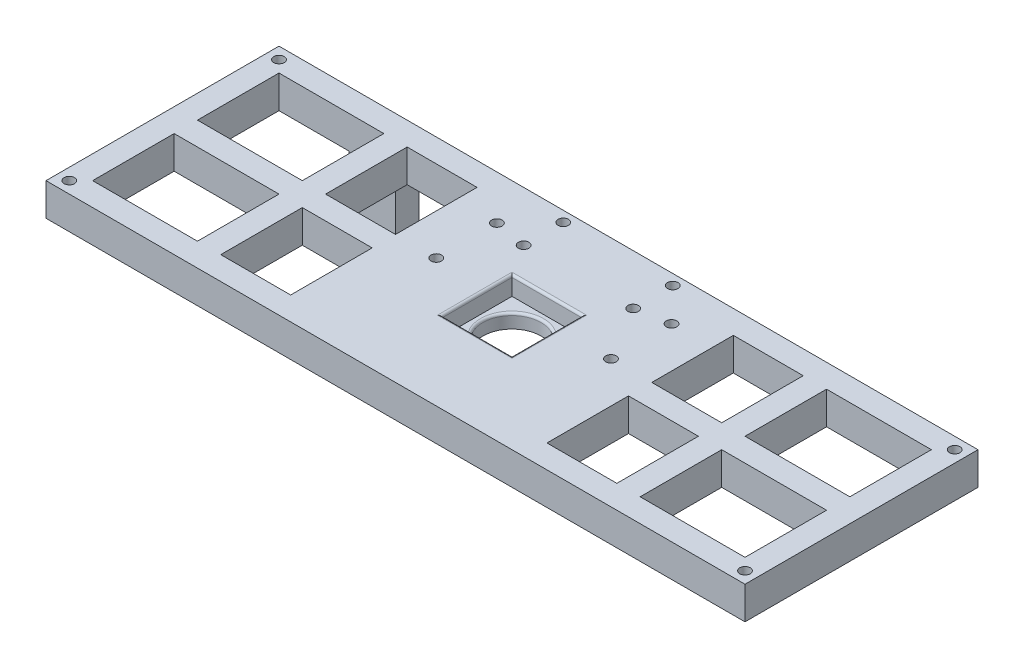
SolidWorks part; units mm, degrees
ref_plane "前视基准面" through (0, 0, 0) normal (0, 0, 1) x (1, 0, 0)
ref_plane "上视基准面" through (0, 0, 0) normal (0, 1, 0) x (1, 0, 0)
ref_plane "右视基准面" through (0, 0, 0) normal (1, 0, 0) x (0, 0, -1)
sketch "草图1" plane through (0, 0, 0) normal (0, 1, 0) x (1, 0, 0)
  line L1 (0, 0) -> (-300, 0)
  line L2 (0, 0) -> (0, 100)
  line L3 (0, 100) -> (-300, 100)
  line L4 (-300, 0) -> (-300, 100)
  dimension "D1" = 300
  dimension "D2" = 100
extrude "凸台-拉伸1" add sketch "草图1" along normal blind 16
sketch "草图2" plane through (0, 16, 0) normal (0, 1, 0) x (1, 0, 0)
  line L0 (-150, 100) -> (-150, 50) construction
  line L1 (0, 100) -> (-300, 100) construction
  line L2 (-300, 50) -> (-150, 50) construction
  line L3 (-300, 100) -> (-300, 0) construction
  line L5 (-165, 65) -> (-135, 65)
  line L6 (-165, 65) -> (-165, 35)
  line L7 (-165, 35) -> (-135, 35)
  line L8 (-135, 65) -> (-135, 35)
  line L9 (-165, 65) -> (-135, 35) construction
  line L10 (-165, 35) -> (-135, 65) construction
  dimension "D1" = 50
  dimension "D2" = 30
  dimension "D3" = 30
extrude "切除-拉伸1" cut sketch "草图2" against normal blind 8
sketch "草图3" plane through (0, 8, 0) normal (0, 1, 0) x (1, 0, 0)
  line L0 (-135, 65) -> (-165, 65) construction
  line L1 (-135, 35) -> (-135, 65) construction
  circle A0 centre (-150, 50) radius 12.5
  dimension "D3" = 25
  dimension "D1" = 15
  dimension "D2" = 15
extrude "切除-拉伸2" cut sketch "草图3" against normal blind 14
sketch "草图4" plane through (0, 16, 0) normal (0, 1, 0) x (1, 0, 0)
  line L0 (-165, 65) -> (-165, 35) construction
  line L1 (-295, 90) -> (-245, 90)
  line L2 (-295, 90) -> (-295, 55)
  line L3 (-295, 55) -> (-245, 55)
  line L4 (-245, 90) -> (-245, 55)
  line L5 (-295, 45) -> (-245, 45)
  line L6 (-295, 45) -> (-295, 10)
  line L7 (-295, 10) -> (-245, 10)
  line L8 (-245, 45) -> (-245, 10)
  line L9 (-235, 90) -> (-185, 90)
  line L10 (-235, 90) -> (-235, 55)
  line L11 (-235, 55) -> (-185, 55)
  line L12 (-185, 90) -> (-185, 55)
  line L13 (-235, 45) -> (-185, 45)
  line L14 (-235, 45) -> (-235, 10)
  line L15 (-235, 10) -> (-185, 10)
  line L16 (-185, 45) -> (-185, 10)
  line L17 (0, 100) -> (-300, 100) construction
  line L18 (-300, 0) -> (0, 0) construction
  line L19 (-300, 100) -> (-300, 0) construction
  line L20 (-150, 100) -> (-150, 73.2626) construction
  line L21 (-5, 10) -> (-55, 10)
  line L22 (-55, 45) -> (-55, 10)
  line L23 (-5, 45) -> (-55, 45)
  line L24 (-5, 45) -> (-5, 10)
  line L25 (-65, 10) -> (-115, 10)
  line L26 (-115, 45) -> (-115, 10)
  line L27 (-65, 45) -> (-115, 45)
  line L28 (-65, 45) -> (-65, 10)
  line L29 (-65, 55) -> (-115, 55)
  line L30 (-115, 90) -> (-115, 55)
  line L31 (-65, 90) -> (-115, 90)
  line L32 (-65, 90) -> (-65, 55)
  line L33 (-5, 55) -> (-55, 55)
  line L34 (-55, 90) -> (-55, 55)
  line L35 (-5, 90) -> (-55, 90)
  line L36 (-5, 90) -> (-5, 55)
  dimension "D1" = 20
  dimension "D2" = 20
  dimension "D3" = 10
  dimension "D4" = 10
  dimension "D5" = 10
  dimension "D6" = 35
  dimension "D7" = 10
  dimension "D8" = 10
  dimension "D9" = 5
  dimension "D10" = 5
  dimension "D11" = 35
  dimension "D12" = 35
  dimension "D13" = 50
  dimension "D14" = 50
  dimension "D15" = 50
  dimension "D16" = 50
extrude "切除-拉伸3" cut sketch "草图4" against normal up to next
sketch "草图7" plane through (-185, 0, 0) normal (-1, 0, 0) x (0, 0, 1)
  line L0 (-45, 0) -> (-10, 0) construction
  line L1 (-10, 0) -> (-10, 16) construction
  line L2 (-10, 16) -> (-45, 16) construction
  line L3 (-45, 16) -> (-45, 0) construction
  line L4 (-90, 0) -> (-55, 0) construction
  line L5 (-55, 0) -> (-55, 16) construction
  line L6 (-55, 16) -> (-90, 16) construction
  line L7 (-90, 16) -> (-90, 0) construction
  line L8 (-45, 0) -> (-10, 0)
  line L9 (-10, 0) -> (-10, 16)
  line L10 (-10, 16) -> (-45, 16)
  line L11 (-45, 16) -> (-45, 0)
  line L12 (-90, 0) -> (-55, 0)
  line L13 (-55, 0) -> (-55, 16)
  line L14 (-55, 16) -> (-90, 16)
  line L15 (-90, 16) -> (-90, 0)
extrude "凸台-拉伸2" add sketch "草图7" along normal blind 20
sketch "草图8" plane through (-115, 0, 0) normal (1, 0, 0) x (0, 0, -1)
  line L0 (10, 0) -> (45, 0) construction
  line L1 (45, 0) -> (45, 16) construction
  line L2 (45, 16) -> (10, 16) construction
  line L3 (10, 16) -> (10, 0) construction
  line L4 (55, 0) -> (90, 0) construction
  line L5 (90, 0) -> (90, 16) construction
  line L6 (90, 16) -> (55, 16) construction
  line L7 (55, 16) -> (55, 0) construction
  line L8 (10, 0) -> (45, 0)
  line L9 (45, 0) -> (45, 16)
  line L10 (45, 16) -> (10, 16)
  line L11 (10, 16) -> (10, 0)
  line L12 (55, 0) -> (90, 0)
  line L13 (90, 0) -> (90, 16)
  line L14 (90, 16) -> (55, 16)
  line L15 (55, 16) -> (55, 0)
extrude "凸台-拉伸3" add sketch "草图8" along normal blind 20
sketch "草图9" plane through (0, 0, 0) normal (0, -1, 0) x (1, 0, 0)
  line L5 (-295, -90) -> (-245, -90) construction
  line L10 (-260, -90) -> (-240, -90)
  line L20 (-260, -90) -> (-260, -100)
  line L21 (-260, -100) -> (-240, -100)
  line L22 (-240, -90) -> (-240, -100)
  line L23 (0, -100) -> (-300, -100) construction
  line L24 (-300, -100) -> (-300, 0) construction
  dimension "D3" = 20
  dimension "D4" = 40
extrude "凸台-拉伸4" add sketch "草图9" along normal blind 25
fillet "圆角1" radius 1 1 edges at (-150, 8, -37.5)
fillet "圆角2" radius 1 4 edges at (-135, 16, -50) (-150, 16, -65) (-150, 16, -35) (-165, 16, -50)
sketch "草图13" plane through (-5, 0, 0) normal (-1, 0, 0) x (0, 0, 1)
  line L0 (-90, 0) -> (-55, 0) construction
  line L1 (-55, 0) -> (-55, 16) construction
  line L2 (-55, 16) -> (-90, 16) construction
  line L3 (-90, 16) -> (-90, 0) construction
  line L4 (-45, 0) -> (-10, 0) construction
  line L5 (-10, 0) -> (-10, 16) construction
  line L6 (-10, 16) -> (-45, 16) construction
  line L7 (-45, 16) -> (-45, 0) construction
  line L8 (-90, 0) -> (-55, 0)
  line L9 (-55, 0) -> (-55, 16)
  line L10 (-55, 16) -> (-90, 16)
  line L11 (-90, 16) -> (-90, 0)
  line L12 (-45, 0) -> (-10, 0)
  line L13 (-10, 0) -> (-10, 16)
  line L14 (-10, 16) -> (-45, 16)
  line L15 (-45, 16) -> (-45, 0)
extrude "凸台-拉伸6" add sketch "草图13" along normal blind 4
sketch "草图14" plane through (-295, 0, 0) normal (1, 0, 0) x (0, 0, -1)
  line L0 (55, 0) -> (90, 0) construction
  line L1 (90, 0) -> (90, 16) construction
  line L2 (90, 16) -> (55, 16) construction
  line L3 (55, 16) -> (55, 0) construction
  line L4 (10, 0) -> (45, 0) construction
  line L5 (45, 0) -> (45, 16) construction
  line L6 (45, 16) -> (10, 16) construction
  line L7 (10, 16) -> (10, 0) construction
  line L8 (55, 0) -> (90, 0)
  line L9 (90, 0) -> (90, 16)
  line L10 (90, 16) -> (55, 16)
  line L11 (55, 16) -> (55, 0)
  line L12 (10, 0) -> (45, 0)
  line L13 (45, 0) -> (45, 16)
  line L14 (45, 16) -> (10, 16)
  line L15 (10, 16) -> (10, 0)
extrude "凸台-拉伸7" add sketch "草图14" along normal blind 4
sketch "草图17" plane through (-291, 0, 0) normal (1, 0, 0) x (0, 0, -1)
  line L0 (10, 16) -> (10, 0) construction
  line L1 (10, 0) -> (45, 0) construction
  line L2 (45, 0) -> (45, 16) construction
  line L3 (45, 16) -> (10, 16) construction
  line L4 (55, 16) -> (55, 0) construction
  line L5 (55, 0) -> (90, 0) construction
  line L6 (90, 0) -> (90, 16) construction
  line L7 (90, 16) -> (55, 16) construction
  line L8 (10, 16) -> (10, 0)
  line L9 (10, 0) -> (45, 0)
  line L10 (45, 0) -> (45, 16)
  line L11 (45, 16) -> (10, 16)
  line L12 (55, 16) -> (55, 0)
  line L13 (55, 0) -> (90, 0)
  line L14 (90, 0) -> (90, 16)
  line L15 (90, 16) -> (55, 16)
extrude "凸台-拉伸8" add sketch "草图17" along normal blind 1
sketch "草图18" plane through (-9, 0, 0) normal (-1, 0, 0) x (0, 0, 1)
  line L0 (-45, 16) -> (-45, 0) construction
  line L1 (-45, 0) -> (-10, 0) construction
  line L2 (-10, 0) -> (-10, 16) construction
  line L3 (-10, 16) -> (-45, 16) construction
  line L4 (-90, 16) -> (-90, 0) construction
  line L5 (-90, 0) -> (-55, 0) construction
  line L6 (-55, 0) -> (-55, 16) construction
  line L7 (-55, 16) -> (-90, 16) construction
  line L8 (-45, 16) -> (-45, 0)
  line L9 (-45, 0) -> (-10, 0)
  line L10 (-10, 0) -> (-10, 16)
  line L11 (-10, 16) -> (-45, 16)
  line L12 (-90, 16) -> (-90, 0)
  line L13 (-90, 0) -> (-55, 0)
  line L14 (-55, 0) -> (-55, 16)
  line L15 (-55, 16) -> (-90, 16)
extrude "凸台-拉伸9" add sketch "草图18" along normal blind 1
sketch "草图19" plane through (0, 16, 0) normal (0, 1, 0) x (1, 0, 0)
  line L0 (-300, 100) -> (-295, 100) construction
  line L1 (0, 100) -> (-300, 100) construction
  line L2 (-295, 100) -> (-295, 95) construction
  line L3 (-150, 100) -> (-150, 83.4567) construction
  line L4 (-300, 50) -> (-202.8605, 50) construction
  line L5 (-300, 100) -> (-300, 0) construction
  line L6 (-150, 0) -> (-150, 22.48) construction
  line L7 (-300, 0) -> (0, 0) construction
  line L8 (-5, 100) -> (-5, 95) construction
  line L9 (0, 100) -> (-5, 100) construction
  circle A0 centre (-295, 95) radius 2.25
  circle A1 centre (-295, 5) radius 2.25
  circle A4 centre (-5, 5) radius 2.25
  circle A5 centre (-5, 95) radius 2.25
  dimension "D3" = 4.5
  dimension "D1" = 5
  dimension "D2" = 5
extrude "切除-拉伸8" cut sketch "草图19" against normal blind 5
sketch "草图20" plane through (0, 0, 0) normal (0, -1, 0) x (1, 0, 0)
  circle A2 centre (-295, -95) radius 2.25 construction
  circle A3 centre (-295, -5) radius 2.25 construction
  circle A6 centre (-295, -95) radius 2.25
  circle A7 centre (-295, -5) radius 2.25
  circle A8 centre (-5, -95) radius 2.25 construction
  circle A9 centre (-5, -5) radius 2.25 construction
  circle A10 centre (-5, -95) radius 2.25
  circle A11 centre (-5, -5) radius 2.25
extrude "切除-拉伸9" cut sketch "草图20" against normal blind 7
extrude "切除-拉伸10" cut sketch "草图21" against normal blind 5
sketch "草图21" plane through (-100.2762, 16, -200.0918) normal (0, 1, 0) x (-0.0018, 0, -1)
  circle A4 centre (-104.5433, 26.4163) radius 1.45
  circle A5 centre (-121.5433, 26.4476) radius 1.45
  circle A6 centre (-121.4568, 73.4475) radius 1.45
  circle A7 centre (-104.4568, 73.4162) radius 1.45
sketch "草图22" plane through (0, 16, 0) normal (0, 1, 0) x (1, 0, 0)
  circle A0 centre (-173.5, 95.5) radius 2.25
  circle A1 centre (-173.5, 78.5) radius 2.25
  circle A2 centre (-126.5, 95.5) radius 2.25
  circle A3 centre (-126.5, 78.5) radius 2.25
  dimension "D1" = 4.5
  dimension "D2" = 4.5
  dimension "D3" = 4.5
  dimension "D4" = 4.5
extrude "切除-拉伸11" cut sketch "草图22" against normal blind 5
extrude "切除-拉伸12" cut sketch "草图23" against normal blind 5
sketch "草图23" plane through (-100.2762, 16, -200.0918) normal (0, 1, 0) x (-0.0018, 0, -1)
  circle A4 centre (-119.0691, 12.4622) radius 1.45
  circle A5 centre (-145.069, 12.51) radius 1.45
  circle A6 centre (-144.931, 87.4716) radius 1.45
  circle A7 centre (-118.9311, 87.4237) radius 1.45
sketch "草图24" plane through (0, 16, 0) normal (0, 1, 0) x (1, 0, 0)
  circle A0 centre (-187.4808, 81) radius 2.25
  circle A1 centre (-187.4808, 55) radius 2.25
  circle A2 centre (-112.5192, 81) radius 2.25
  circle A3 centre (-112.5192, 55) radius 2.25
  dimension "D1" = 4.5
  dimension "D2" = 4.5
  dimension "D3" = 4.5
  dimension "D4" = 4.5
extrude "切除-拉伸13" cut sketch "草图24" against normal blind 5
sketch "草图26" plane through (0, 0, 0) normal (0, -1, 0) x (1, 0, 0)
  line L12 (-260, -90) -> (-290, -90)
  line L13 (-290, -90) -> (-290, -55)
  line L14 (-290, -55) -> (-245, -55)
  line L15 (-245, -55) -> (-245, -90)
  line L16 (-245, -90) -> (-240, -90)
  line L17 (-240, -90) -> (-240, -100)
  line L18 (-240, -100) -> (0, -100)
  line L19 (0, -100) -> (0, 0)
  line L20 (0, 0) -> (-300, 0)
  line L21 (-300, 0) -> (-300, -100)
  line L22 (-300, -100) -> (-260, -100)
  line L23 (-260, -100) -> (-260, -90)
  line L24 (-260, -90) -> (-290, -90)
  line L25 (-290, -90) -> (-290, -55)
  line L26 (-290, -55) -> (-245, -55)
  line L27 (-245, -55) -> (-245, -90)
  line L28 (-245, -90) -> (-240, -90)
  line L29 (-240, -90) -> (-240, -100)
  line L30 (-240, -100) -> (0, -100)
  line L31 (0, -100) -> (0, 0)
  line L32 (0, 0) -> (-300, 0)
  line L33 (-300, 0) -> (-300, -100)
  line L34 (-300, -100) -> (-260, -100)
  line L35 (-260, -100) -> (-260, -90)
  dimension "D1" = 0
extrude "切除-拉伸15" cut sketch "草图26" against normal blind 2
